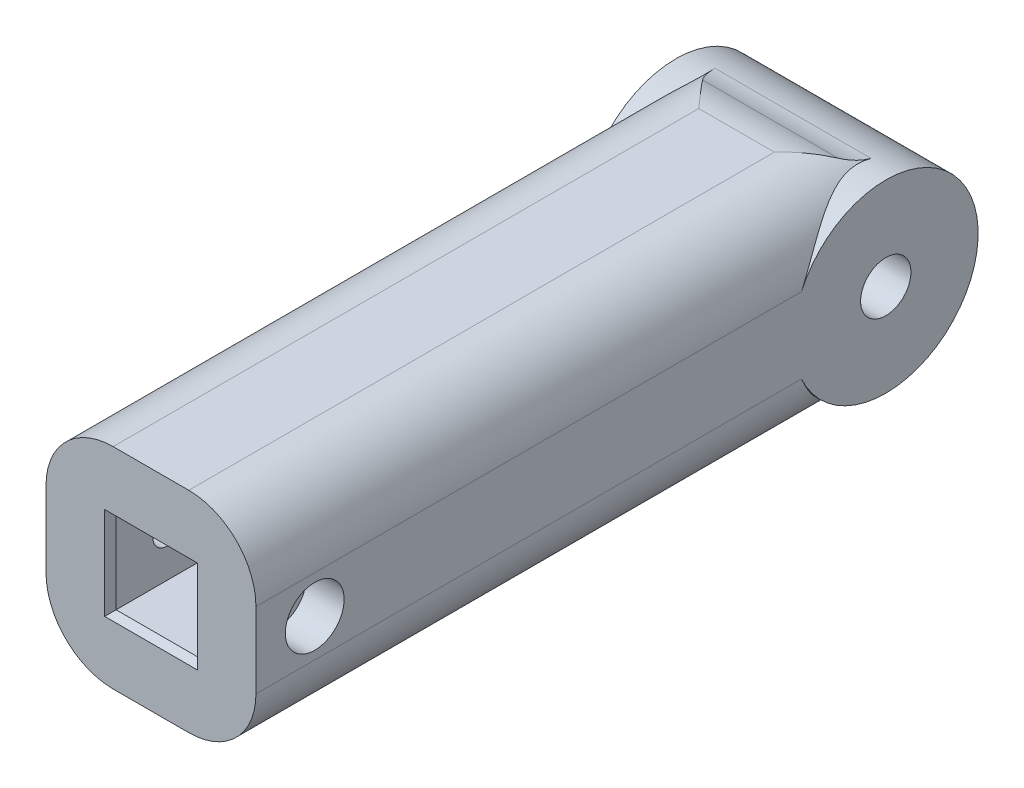
SolidWorks part; units mm, degrees
ref_plane "Спереди" through (0, 0, 0) normal (0, 0, 1) x (1, 0, 0)
ref_plane "Сверху" through (0, 0, 0) normal (0, 1, 0) x (1, 0, 0)
ref_plane "Справа" through (0, 0, 0) normal (1, 0, 0) x (0, 0, -1)
sketch "Sketch2" plane through (0, 0, 0) normal (0, 0, 1) x (1, 0, 0)
  line L1 (12.5, -12.5) -> (-12.5, -12.5)
  line L2 (12.5, -12.5) -> (12.5, 12.5)
  line L3 (12.5, 12.5) -> (-12.5, 12.5)
  line L4 (-12.5, -12.5) -> (-12.5, 12.5)
  line L5 (12.5, -12.5) -> (-12.5, 12.5) construction
  line L6 (12.5, 12.5) -> (-12.5, -12.5) construction
  line L7 (5.15, -5.15) -> (-5.15, -5.15)
  line L8 (5.15, -5.15) -> (5.15, 5.15)
  line L9 (5.15, 5.15) -> (-5.15, 5.15)
  line L10 (-5.15, -5.15) -> (-5.15, 5.15)
  line L11 (5.15, -5.15) -> (-5.15, 5.15) construction
  line L12 (5.15, 5.15) -> (-5.15, -5.15) construction
  point P0 (0, 0)
  point P6 (0, 0)
  dimension "D1" = 25
  dimension "D2" = 10.3
extrude "Boss-Extrude1" add sketch "Sketch2" along normal blind 85
fillet "Fillet1" radius 8 4 edges at (12.5, -12.5, 42.5) (12.5, 12.5, 42.5) (-12.5, -12.5, 42.5) (-12.5, 12.5, 42.5)
sketch "Sketch3" plane through (-12.5, 0, 0) normal (-1, 0, 0) x (0, 0, 1)
  line L0 (0, 0) -> (85, 0) construction
  line L1 (0, 4.5) -> (0, -4.5) construction
  line L2 (85, 4.5) -> (85, -4.5) construction
  circle A0 centre (10, 0) radius 3
  dimension "D1" = 6
  dimension "D2" = 10
extrude "Cut-Extrude1" cut sketch "Sketch3" against normal through all
sketch "Sketch4" plane through (5.15, 0, 0) normal (-1, 0, 0) x (0, 0, 1)
  circle A0 centre (10, 0) radius 11
  circle A1 centre (10, 0) radius 3
  circle A2 centre (10, 0) radius 3 construction
  dimension "D1" = 22
extrude "Boss-Extrude2" add sketch "Sketch4" against normal up to surface (7.35 mm away) up to face at (12.5, 0, 13)
sketch "Sketch5" plane through (-5.15, 0, 0) normal (1, 0, 0) x (0, 0, -1)
  circle A0 centre (-10, 0) radius 11
  circle A1 centre (-9.4923, 0) radius 3
  circle A2 centre (-10, 0) radius 3 construction
  dimension "D1" = 22
extrude "Boss-Extrude3" add sketch "Sketch5" against normal up to surface (7.35 mm away) up to face at (-12.5, 0, 13)
sketch "Sketch6" plane through (12.5, 0, 0) normal (1, 0, 0) x (0, 0, -1)
  line L0 (-10, -27.3297) -> (-10, 27.3297) construction
  line L1 (-13, 0) -> (-7, 0) construction
  line L2 (-10, 11) -> (-10, 16.9718)
  line L3 (-10, 16.9718) -> (7.792, 16.9718)
  line L4 (7.792, 16.9718) -> (7.792, -18.6645)
  line L5 (7.792, -18.6645) -> (-10, -18.6645)
  line L6 (-10, -18.6645) -> (-10, -11)
  circle A0 centre (-10, 0) radius 3 construction
  arc A1 (-20.0374, -4.5) -> (-20.0374, 4.5) centre (-10, 0) ccw construction
  arc A2 (-10, 11) -> (-10, -11) centre (-10, 0) cw
  point P4 (-10, 0)
  point P11 (-10, 0)
extrude "Cut-Extrude2" cut sketch "Sketch6" against normal through all
fillet "Fillet2" radius 10 2 edges at (0, -12.5, 10) (0, 12.5, 10)
fillet "Fillet3" radius 10 2 edges at (0, -11, 10) (0, 11, 10)
sketch "Sketch7" plane through (-12.5, 0, 0) normal (-1, 0, 0) x (0, 0, 1)
  line L0 (85, 0) -> (12.4923, 0) construction
  line L1 (85, 4.5) -> (85, -4.5) construction
  line L2 (85, 4.5) -> (20.0374, 4.5) construction
  line L3 (76.375, 2.8146) -> (74.75, 0)
  line L4 (74.75, 0) -> (76.375, -2.8146)
  line L5 (76.375, -2.8146) -> (79.625, -2.8146)
  line L6 (79.625, -2.8146) -> (81.25, 0)
  line L7 (81.25, 0) -> (79.625, 2.8146)
  line L8 (79.625, 2.8146) -> (76.375, 2.8146)
  arc A0 (9.7462, -2.9892) -> (9.7462, 2.9892) centre (9.4923, 0) ccw construction
  circle A1 centre (78, 0) radius 3.25 construction
  dimension "D1" = 6.5
  dimension "D2" = 7
extrude "Cut-Extrude3" cut sketch "Sketch7" against normal blind 4.5
sketch "Sketch8" plane through (-8, 0, 0) normal (-1, 0, 0) x (0, 0, 1)
  line L0 (78, 2.8146) -> (78, -2.8146) construction
  line L1 (79.625, 2.8146) -> (76.375, 2.8146) construction
  line L2 (76.375, -2.8146) -> (79.625, -2.8146) construction
  circle A0 centre (78, 0) radius 1.6
  dimension "D1" = 3.2
extrude "Cut-Extrude4" cut sketch "Sketch8" against normal through all
sketch "Sketch9" plane through (12.5, 0, 0) normal (1, 0, 0) x (0, 0, -1)
  circle A0 centre (-78, 0) radius 3.5
  dimension "D1" = 7
extrude "Cut-Extrude5" cut sketch "Sketch9" against normal blind 4.5
chamfer "Chamfer1" distance 1 angle 20 4 edges at (0, -5.15, 85) (5.15, 0, 85) (-5.15, 0, 85) (0, 5.15, 85)
